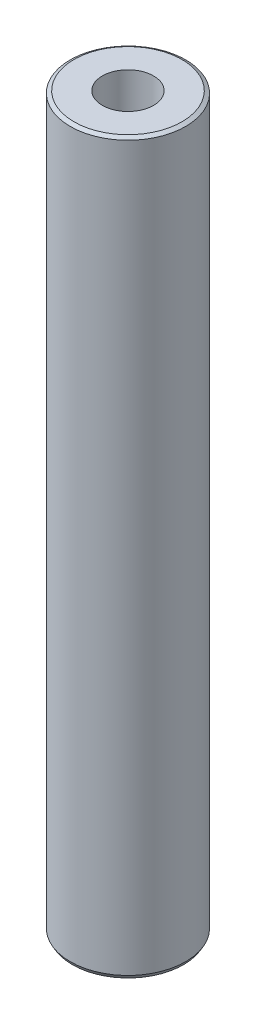
SolidWorks part; units mm, degrees
ref_plane "Front Plane" through (0, 0, 0) normal (0, 0, 1) x (1, 0, 0)
ref_plane "Top Plane" through (0, 0, 0) normal (0, 1, 0) x (1, 0, 0)
ref_plane "Right Plane" through (0, 0, 0) normal (1, 0, 0) x (0, 0, -1)
sketch "Sketch1" plane through (0, 0, 0) normal (0, 1, 0) x (1, 0, 0)
  circle A0 centre (0, 0) radius 47.5
  dimension "SHAFT_OD" = 95
extrude "Boss-Extrude1" add sketch "Sketch1" along normal blind 600
sketch "Sketch2" plane through (0, 0, 0) normal (0, 1, 0) x (1, 0, 0)
  circle A0 centre (0, 0) radius 21.0519
  dimension "BORE_D" = 42.1038
extrude "Cut-Extrude1" cut sketch "Sketch2" along normal through all
chamfer "Chamfer1" distance 1.7754 angle 60 2 edges at (0, 600, 47.5) (0, 0, 47.5) first distance on face at (0, 600, 47.5) first distance on face at (0, 0, 21.0519)
